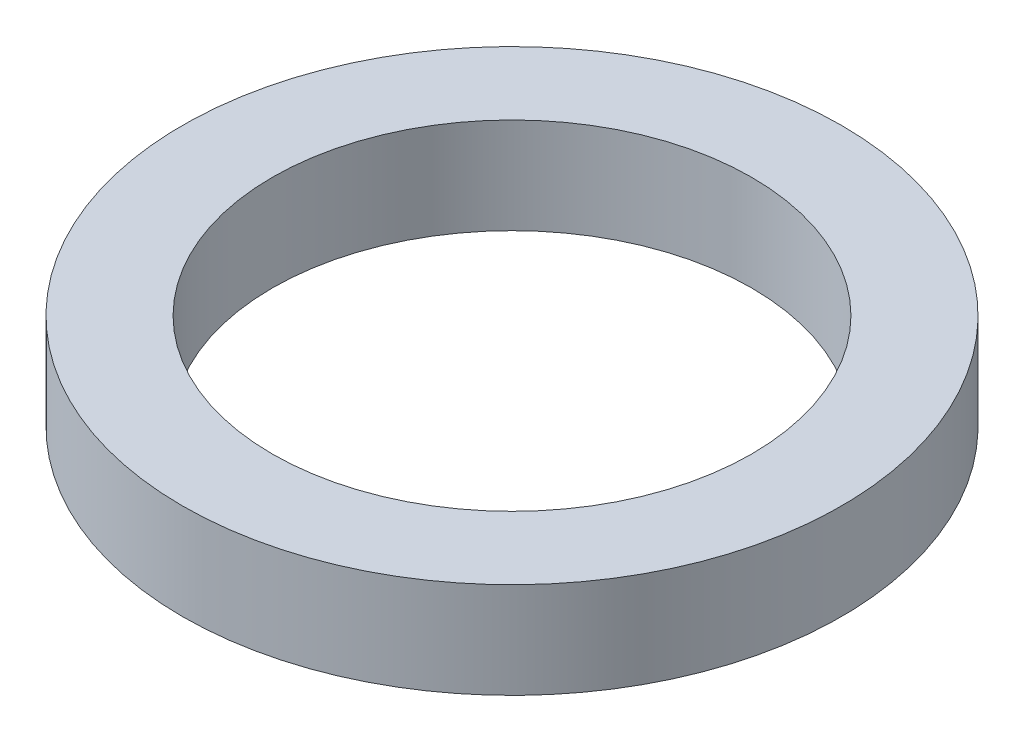
SolidWorks part; units mm, degrees
ref_plane "Front Plane" through (0, 0, 0) normal (0, 0, 1) x (1, 0, 0)
ref_plane "Top Plane" through (0, 0, 0) normal (0, 1, 0) x (1, 0, 0)
ref_plane "Right Plane" through (0, 0, 0) normal (1, 0, 0) x (0, 0, -1)
sketch "Sketch1" plane through (0, 0, 0) normal (0, 1, 0) x (1, 0, 0)
  circle A0 centre (0, 0) radius 27.5
  dimension "FLANGE_OD" = 55
extrude "Boss-Extrude1" add sketch "Sketch1" along normal blind 8
sketch "Sketch2" plane through (0, 0, 0) normal (0, 1, 0) x (1, 0, 0)
  circle A0 centre (0, 0) radius 20
  dimension "BORE_D" = 40
extrude "Cut-Extrude1" cut sketch "Sketch2" along normal through all
sketch "Sketch3" plane through (0, 8, 0) normal (0, 1, 0) x (1, 0, 0)
  circle A0 centre (0, 0) radius 12.1547 construction
  circle A1 centre (-12.1547, 0) radius 1.5
  dimension "BOLT_D" = 3
  dimension "BOLT_PCD" = 24.3094
extrude "Cut-Extrude2" cut sketch "Sketch3" against normal blind 6.8839 rebuild error yes
pattern_circular "CirPattern1" count 5 over 360 rebuild error yes
